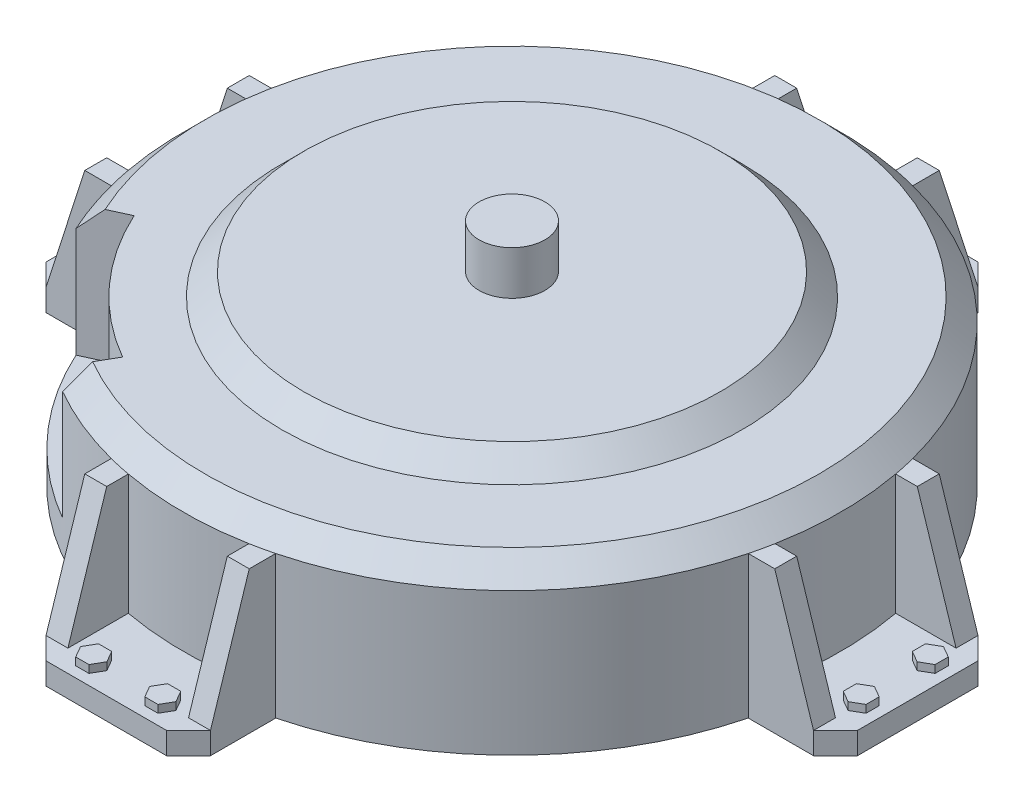
SolidWorks part; units mm, degrees
material "AISI 1045 Steel, cold drawn"
ref_plane "Front Plane" through (0, 0, 0) normal (0, 0, 1) x (1, 0, 0)
ref_plane "Top Plane" through (0, 0, 0) normal (0, 1, 0) x (1, 0, 0)
ref_plane "Right Plane" through (0, 0, 0) normal (1, 0, 0) x (0, 0, -1)
sketch "Sketch1" plane through (0, 0, 0) normal (0, 1, 0) x (1, 0, 0)
  circle A0 centre (0, 0) radius 150
  dimension "D1" = 300
extrude "Boss-Extrude1" add sketch "Sketch1" along normal blind 75
chamfer "Chamfer1" distance 10 angle 45 1 edges at (0, 75, 150)
sketch "Sketch2" plane through (0, 0, 0) normal (0, -1, 0) x (1, 0, 0)
  line L1 (-185, 37.5) -> (-145.2369, 37.5)
  line L2 (-185, 37.5) -> (-185, -37.5)
  line L3 (-185, -37.5) -> (-145.2369, -37.5)
  circle A0 centre (0, 0) radius 150 construction
  circle A1 centre (0, 0) radius 150
  point P0 (-150, 0)
  circle M4 centre (0, 0) radius 150
  dimension "D1" = 75
extrude "Boss-Extrude2" add sketch "Sketch2" against normal blind 10 contours L2 L3 L1 M4 region at (-166.6838, 0, 0)
chamfer "Chamfer2" distance 10 angle 45 2 edges at (-185, 5, -37.5) (-185, 5, 37.5)
sketch "Sketch3" plane through (0, 0, 37.5) normal (0, 0, 1) x (1, 0, 0)
  line L0 (-145.2369, 10) -> (-145.2369, 65)
  line L1 (-150, 65) -> (150, 65) construction
  line L3 (-175, 10) -> (-145.2369, 10)
  line L4 (-145.2369, 65) -> (-157.32, 65)
  line L5 (-157.32, 65) -> (-175, 10)
  dimension "D1" = 17.68
extrude "Boss-Extrude3" add sketch "Sketch3" against normal blind 10
sketch "Sketch4" plane through (0, 10, 0) normal (0, 1, 0) x (1, 0, 0)
  line L0 (-175, 37.5) -> (-175, -37.5) construction
  line L8 (-175, -21.7491) -> (-169.8038, -18.7491)
  line L9 (-169.8038, -18.7491) -> (-169.8038, -12.7491)
  line L10 (-169.8038, -12.7491) -> (-175, -9.7491)
  line L11 (-175, -9.7491) -> (-180.1962, -12.7491)
  line L12 (-180.1962, -12.7491) -> (-180.1962, -18.7491)
  line L13 (-180.1962, -18.7491) -> (-175, -21.7491)
  circle A0 centre (-175, -15.7491) radius 5.1962 construction
  dimension "D1" = 6
extrude "Boss-Extrude4" add sketch "Sketch4" along normal blind 3.5
mirror "Mirror1" about plane through (0, 0, 0) normal (0, 0, 1) of "Boss-Extrude3", "Boss-Extrude4"
pattern_circular "CirPattern1" count 4 over 360 about axis through (0, 0, 0) along (0, 1, 0) of "Boss-Extrude2", "Chamfer2", "Mirror1"
sketch "Sketch5" plane through (0, 75, 0) normal (0, 1, 0) x (1, 0, 0)
  line L1 (0, 0) -> (0, -205.9545) construction
  line L2 (-118.2007, -54.1165) -> (-136.3854, -62.4421)
  line L3 (-65, -112.5833) -> (-75, -129.9038)
  arc A1 (-145.2369, -37.5) -> (-37.5, -145.2369) centre (0, 0) ccw construction
  arc A3 (-136.3854, -62.4421) -> (-75, -129.9038) centre (0, 0) ccw
  circle A4 centre (0, 0) radius 130
  circle M7 centre (0, 0) radius 140
  dimension "D3" = 260
  dimension "D2" = 30
extrude "Cut-Extrude2" cut sketch "Sketch5" against normal blind 60 contours L2 A3 L3 M7 | A4 L2 L3 M7 region at (-98.3145, 75, 89.4593) region at (-105.5906, 75, 96.0801)
sketch "Sketch6" plane through (0, 75, 0) normal (0, 1, 0) x (1, 0, 0)
  circle A0 centre (0, 0) radius 110
  dimension "D1" = 220
extrude "Boss-Extrude5" add sketch "Sketch6" along normal blind 10
chamfer "Chamfer3" distance 15 angle 45 1 edges at (0, 85, 110)
sketch "Sketch7" plane through (0, 85, 0) normal (0, 1, 0) x (1, 0, 0)
  circle A0 centre (0, 0) radius 15
  dimension "D1" = 30
extrude "Boss-Extrude6" add sketch "Sketch7" along normal blind 20
